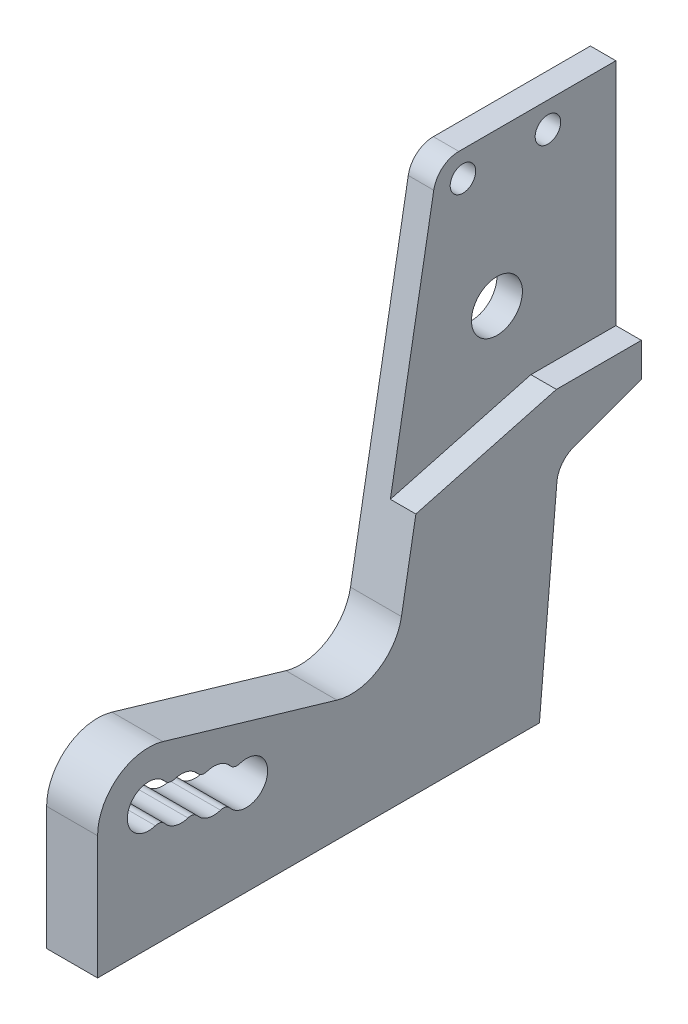
SolidWorks part; units mm, degrees
material "1060 Alloy"
ref_plane "Front Plane" through (0, 0, 0) normal (0, 0, 1) x (1, 0, 0)
ref_plane "Top Plane" through (0, 0, 0) normal (0, 1, 0) x (1, 0, 0)
ref_plane "Right Plane" through (0, 0, 0) normal (1, 0, 0) x (0, 0, -1)
sketch "Sketch1" plane through (0, 0, 0) normal (1, 0, 0) x (0, 0, -1)
  line L1 (0, 0) -> (64, 0)
  line L2 (0, 0) -> (0, 60)
  line L3 (0, 60) -> (64, 60)
  line L4 (64, 0) -> (64, 60)
  circle A0 centre (6, 14.5) radius 2.5
  circle A1 centre (50, 42) radius 3
  dimension "D1" = 6
  dimension "D2" = 5
  dimension "D3" = 14.5
  dimension "D4" = 6
  dimension "D5" = 42
  dimension "D6" = 50
  dimension "D7" = 64
  dimension "D8" = 60
extrude "Boss-Extrude1" add sketch "Sketch1" along normal blind 6
sketch "Sketch3" plane through (6, 0, 0) normal (1, 0, 0) x (0, 0, -1)
  line L57 (64, 0) -> (52, 0)
  line L58 (64, 0) -> (64, 29)
  line L59 (64, 29) -> (54.2259, 25.4425)
  line L60 (52, 0) -> (54.2259, 25.4425)
  dimension "D1" = 70
  dimension "D2" = 29
  dimension "D3" = 52
  dimension "D4" = 85
extrude "Cut-Extrude2" cut sketch "Sketch3" against normal up to next
fillet "Fillet2" radius 3 1 edges at (3, 25.4425, -54.2259)
hole_wizard "Tap Drill for M3 Tap1" positions "Sketch5" profile "Sketch4" hole size "M3" standard "ISO"
sketch "Sketch5" plane through (0, 0, 0) normal (0, -1, 0) x (-1, 0, 0)
  line L0 (0, 0) -> (0, 52) construction
  line L1 (-6, 0) -> (0, 0) construction
  point P0 (-3, 46)
  point P2 (-3, 10)
  dimension "D1" = 3
  dimension "D2" = 10
  dimension "D3" = 36
sketch "Sketch4" plane through (3, 0, -46) normal (1, 0, 0) x (0, 0, -1)
  line L0 (0, 0) -> (0, 9.7511)
  line L1 (0, 9.7511) -> (1.25, 9)
  line L2 (1.25, 9) -> (1.25, 0)
  line L5 (1.25, 0) -> (0, 0)
  line L10 (0, 9.7511) -> (-1.25, 9) construction
  line L11 (0, -6.35) -> (0, 107.95) construction
  dimension "Hole Dia." = 2.5
  dimension "Hole Depth" = 9
  dimension "Drill Angle" = 118
sketch "Sketch9" plane through (6, 0, 0) normal (1, 0, 0) x (0, 0, -1)
  line L0 (7.691, 20.2568) -> (28.1634, 14.2432)
  line L1 (0, 0) -> (52, 0) construction
  line L19 (43, 60) -> (35.7632, 18.9581)
  line L21 (0, 60) -> (0, 0) construction
  line L22 (43, 60) -> (0, 60)
  line L23 (0, 60) -> (0, 14.5)
  line L24 (0, 60) -> (0, 0) construction
  line L25 (64, 60) -> (0, 60) construction
  arc A0 (35.7632, 18.9581) -> (28.1634, 14.2432) centre (29.8544, 20) cw
  arc A12 (0, 14.5) -> (7.691, 20.2568) centre (6, 14.5) cw
  circle A16 centre (6, 14.5) radius 2.5 construction
  dimension "D1" = 43
  dimension "D2" = 80
  dimension "D3" = 20
extrude "Cut-Extrude3" cut sketch "Sketch9" against normal blind 8
sketch "Sketch13" plane through (6, 0, 0) normal (1, 0, 0) x (0, 0, -1)
  line L0 (64, 29) -> (64, 60) construction
  line L1 (54, 33) -> (64, 33)
  line L2 (64, 60) -> (43, 60) construction
  line L3 (64, 60) -> (43, 60)
  line L4 (64, 33) -> (64, 60)
  line L5 (35.7632, 18.9581) -> (43, 60) construction
  line L11 (43, 60) -> (37.4576, 28.5675)
  line L15 (37.4576, 28.5675) -> (54, 33)
  dimension "D1" = 10
  dimension "D2" = 65
  dimension "D3" = 27
extrude "Cut-Extrude4" cut sketch "Sketch13" against normal blind 3
fillet "Fillet3" radius 3 1 edges at (1.5, 60, -43)
sketch "Sketch14" plane through (3, 0, 0) normal (1, 0, 0) x (0, 0, -1)
  line L0 (64, 33) -> (64, 60) construction
  line L1 (64, 60) -> (45.5173, 60) construction
  circle A0 centre (56, 57) radius 1.5
  circle A1 centre (46, 57) radius 1.5
  dimension "D1" = 3
  dimension "D2" = 10
  dimension "D3" = 8
  dimension "D4" = 3
extrude "Cut-Extrude5" cut sketch "Sketch14" against normal up to next
sketch "Sketch15" plane through (0, 0, 0) normal (-1, 0, 0) x (0, 0, 1)
  line L0 (-6, 14.5) -> (-26.4724, 8.4864) construction
  line L1 (-28.1634, 14.2432) -> (-7.691, 20.2568) construction
  circle A0 centre (-9.8379, 13.3727) radius 2.5
  circle A1 centre (-6, 14.5) radius 2.5 construction
  dimension "D1" = 4
extrude "Cut-Extrude6" cut sketch "Sketch15" against normal up to next
pattern_linear "LPattern3" count 3 spacing 4 along (0, -0.2818, -0.9595) of "Cut-Extrude6"
fillet "Fillet4" radius 1 6 edges at (3, 12.4971, -7.4962) (3, 11.3698, -11.334) (3, 10.2425, -15.1719) (3, 13.1209, -16.0174) (3, 14.2482, -12.1795) (3, 15.3755, -8.3417)
